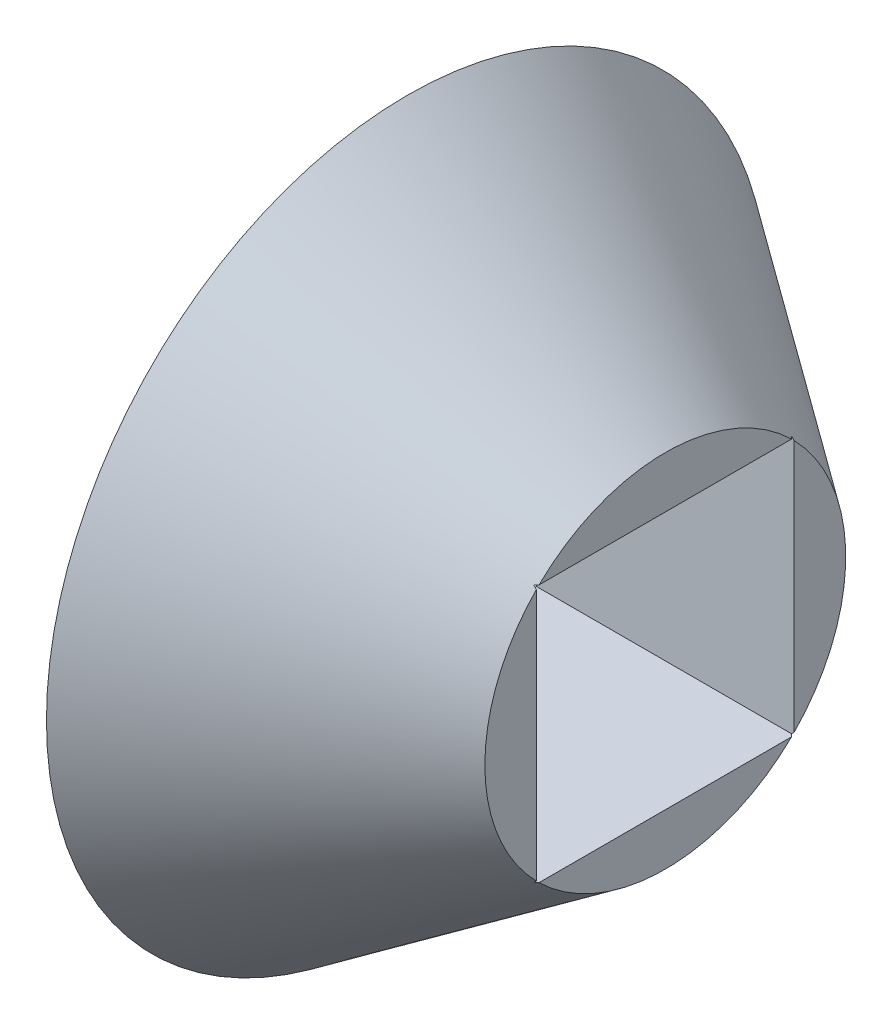
SolidWorks part; units mm, degrees
material "Custom Plastic"
ref_plane "Front Plane" through (0, 0, 0) normal (0, 0, 1) x (1, 0, 0)
ref_plane "Top Plane" through (0, 0, 0) normal (0, 1, 0) x (1, 0, 0)
ref_plane "Right Plane" through (0, 0, 0) normal (1, 0, 0) x (0, 0, -1)
sketch "Sketch1" plane through (0, 0, 0) normal (1, 0, 0) x (0, 0, -1)
  line L1 (1.5875, -1.5875) -> (-1.5875, -1.5875)
  line L2 (1.5875, -1.5875) -> (1.5875, 1.5875)
  line L3 (1.5875, 1.5875) -> (-1.5875, 1.5875)
  line L4 (-1.5875, -1.5875) -> (-1.5875, 1.5875)
  line L5 (1.5875, -1.5875) -> (-1.5875, 1.5875) construction
  line L6 (1.5875, 1.5875) -> (-1.5875, -1.5875) construction
  circle A0 centre (0, 0) radius 4.445
  dimension "D2" = 8.89
  dimension "D1" = 3.175
extrude "Boss-Extrude1" add sketch "Sketch1" along normal blind 3.175
sketch "Sketch2" plane through (0, 0, 0) normal (0, 0, 1) x (1, 0, 0)
  line L0 (0, 4.445) -> (3.175, 4.445)
  line L1 (0, 4.445) -> (0, -4.445) construction
  line L2 (3.175, 4.445) -> (0, 4.445) construction
  line L3 (3.175, -4.445) -> (3.175, 4.445) construction
  line L4 (3.175, 4.445) -> (3.175, 2.2218)
  line L5 (3.175, 2.2218) -> (0, 4.445)
  line L6 (0, 0) -> (3.175, 0) construction
  dimension "D1" = 35
revolve "Cut-Revolve1" cut sketch "Sketch2" angle 360 about L6
